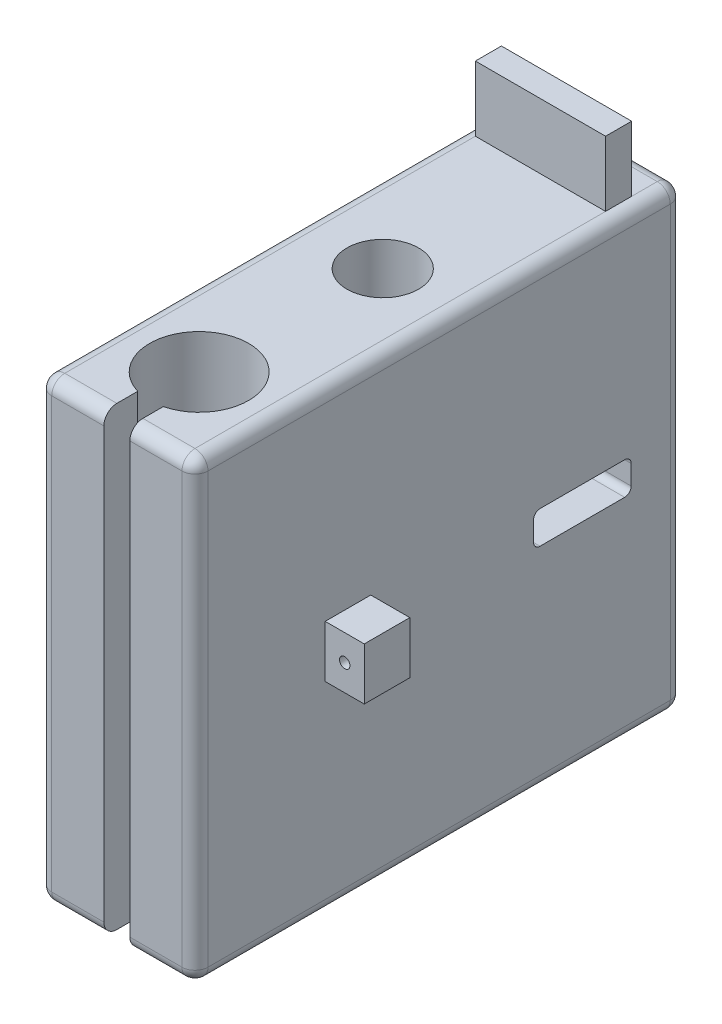
SolidWorks part; units mm, degrees
ref_plane "Front Plane" through (0, 0, 0) normal (0, 0, 1) x (1, 0, 0)
ref_plane "Top Plane" through (0, 0, 0) normal (0, 1, 0) x (1, 0, 0)
ref_plane "Right Plane" through (0, 0, 0) normal (1, 0, 0) x (0, 0, -1)
ref_plane "Plano1" through (-220, 0, 0) normal (1, 0, 0) x (0, 0, -1)
sketch "Esboço1" plane through (-220, 0, 0) normal (1, 0, 0) x (0, 0, -1)
  line L0 (-460.4999, 246.154) -> (-460.4999, 230.354) construction
  line L1 (-465.4999, 248.254) -> (-390.4999, 248.254)
  line L2 (-465.4999, 248.254) -> (-465.4999, 178.254)
  line L3 (-465.4999, 178.254) -> (-390.4999, 178.254)
  line L4 (-390.4999, 248.254) -> (-390.4999, 178.254)
  dimension "D1" = 75
  dimension "D2" = 70
  dimension "D3" = 5
extrude "Ressalto-extrusão1" add sketch "Esboço1" along normal blind 12 and the other way blind 12
sketch "Esboço3" plane through (0, 248.254, 0) normal (0, 1, 0) x (1, 0, 0)
  line L5 (-232, -465.4999) -> (-208, -465.4999) construction
  line L7 (-220, -465.4999) -> (-218, -465.4999)
  line L10 (-218, -465.4999) -> (-218, -460.3692)
  line L11 (-220, -465.4999) -> (-222, -465.4999)
  line L14 (-222, -465.4999) -> (-222, -460.292)
  arc A3 (-218, -460.3692) -> (-222, -460.292) centre (-219.8586, -452.9999) ccw
  circle A8 centre (-219.5085, -425.1499) radius 5.5
  circle A9 centre (-219.5085, -425.1499) radius 5.5
  dimension "D1" = 15.2
  dimension "D3" = 2
  dimension "D4" = 2
  dimension "D2" = 0.5
extrude "Corte-extrusão1" cut sketch "Esboço3" against normal through all
sketch "Esboço4" plane through (0, 0, 390.4999) normal (0, 0, -1) x (-1, 0, 0)
  line L0 (220, 248.254) -> (220, 178.254) construction
  line L1 (232, 248.254) -> (208, 248.254) construction
  line L2 (232, 178.254) -> (208, 178.254) construction
  circle A0 centre (219.8586, 238.254) radius 4.1
  circle A1 centre (219.8586, 188.254) radius 4.1
  dimension "D1" = 8.2
  dimension "D2" = 8.2
extrude "Corte-extrusão2" cut sketch "Esboço4" against normal blind 20
fillet "Filete1" radius 2 14 edges at (-227, 178.254, 465.4999) (-213, 178.254, 465.4999) (-213, 248.254, 465.4999) (-227, 248.254, 465.4999) (-208, 178.254, 427.9999) (-208, 248.254, 427.9999) (-208, 213.254, 465.4999) (-232, 178.254, 427.9999) (-232, 213.254, 465.4999) (-232, 248.254, 427.9999) (-220, 248.254, 390.4999) (-220, 178.254, 390.4999) (-208, 213.254, 390.4999) (-232, 213.254, 390.4999)
sketch "Esboço5" plane through (0, 0, 390.4999) normal (0, 0, -1) x (-1, 0, 0)
  line L8 (213.9984, 195.2586) -> (225.9984, 195.2487)
  line L9 (225.9984, 195.2487) -> (226.0279, 231.2487)
  line L10 (226.0279, 231.2487) -> (214.0279, 231.2586)
  line L11 (214.0279, 231.2586) -> (213.9984, 195.2586)
  line L12 (213.9984, 195.2586) -> (225.9984, 195.2487)
  line L13 (225.9984, 195.2487) -> (226.0279, 231.2487)
  line L14 (226.0279, 231.2487) -> (214.0279, 231.2586)
  line L15 (214.0279, 231.2586) -> (213.9984, 195.2586)
  dimension "D1" = 0
extrude "Corte-extrusão3" cut sketch "Esboço5" against normal blind 29
sketch "Esboço6" plane through (-232, 0, 0) normal (-1, 0, 0) x (0, 0, 1)
  line L0 (392.4999, 213.254) -> (463.4999, 213.254) construction
  line L1 (392.4999, 246.254) -> (392.4999, 180.254) construction
  line L2 (463.4999, 180.254) -> (463.4999, 246.254) construction
  line L3 (398.4999, 213.254) -> (413.4999, 213.254) construction
  line L4 (399.4999, 215.754) -> (412.4999, 215.754)
  line L5 (398.4999, 214.754) -> (398.4999, 211.754)
  line L6 (399.4999, 210.754) -> (412.4999, 210.754)
  line L7 (413.4999, 214.754) -> (413.4999, 211.754)
  arc A0 (412.4999, 215.754) -> (413.4999, 214.754) centre (412.4999, 214.754) cw
  arc A1 (412.4999, 210.754) -> (413.4999, 211.754) centre (412.4999, 211.754) ccw
  arc A2 (398.4999, 211.754) -> (399.4999, 210.754) centre (399.4999, 211.754) ccw
  arc A3 (399.4999, 215.754) -> (398.4999, 214.754) centre (399.4999, 214.754) ccw
  point P14 (413.4999, 215.754)
  point P17 (413.4999, 210.754)
  point P22 (398.4999, 215.754)
  dimension "D4" = 1
  dimension "D1" = 5
  dimension "D2" = 15
  dimension "D3" = 6
extrude "Corte-extrusão4" cut sketch "Esboço6" against normal blind 28
sketch "Esboço7" plane through (-208, 0, 0) normal (1, 0, 0) x (0, 0, -1)
  line L0 (-463.4999, 246.254) -> (-463.4999, 180.254) construction
  line L1 (-445.4999, 217.254) -> (-438.4999, 217.254)
  line L2 (-445.4999, 217.254) -> (-445.4999, 209.254)
  line L3 (-445.4999, 209.254) -> (-438.4999, 209.254)
  line L4 (-438.4999, 217.254) -> (-438.4999, 209.254)
  line L5 (-465.4999, 180.254) -> (-465.4999, 246.254) construction
  point P6 (-463.4999, 213.254)
  point P7 (-445.4999, 213.254)
  dimension "D1" = 7
  dimension "D2" = 8
  dimension "D3" = 20
extrude "Ressalto-extrusão2" add sketch "Esboço7" along normal blind 6 and the other way blind 30
ref_point "Ponto1"
sketch "Esboço9" plane through (0, 0, 445.4999) normal (0, 0, 1) x (1, 0, 0)
  line L0 (-205, 217.254) -> (-205, 209.254) construction
  line L3 (-208, 217.254) -> (-202, 217.254) construction
  line L6 (-208, 209.254) -> (-202, 209.254) construction
  line L7 (-208, 213.254) -> (-202, 213.254) construction
  line L8 (-208, 246.254) -> (-208, 180.254) construction
  line L9 (-202, 217.254) -> (-202, 209.254) construction
hole_wizard "Broca de rosquear para tarraxa de M2x0.41" positions "Esboço13" profile "Esboço14" hole size "M2x0.4" standard "Ansi Metric" end condition through all
sketch "Esboço13" plane through (0, 0, 445.4999) normal (0, 0, 1) x (1, 0, 0)
  line L0 (-205, 217.254) -> (-205, 209.254) construction
  point P0 (-205, 213.254)
sketch "Esboço14" plane through (-205, 213.254, 445.4999) normal (1, 0, 0) x (0, -1, 0)
  line L0 (0, 0) -> (0, 55)
  line L1 (0, 55) -> (0.8, 55)
  line L2 (0.8, 55) -> (0.8, 0)
  line L5 (0.8, 0) -> (0, 0)
  line L11 (0, -6.35) -> (0, 107.95) construction
  dimension "Thru Hole Dia." = 1.6
  dimension "Thru Hole Depth" = 55
sketch "Esboço15" plane through (0, 0, 445.4999) normal (0, 0, 1) x (1, 0, 0)
  line L0 (-235, 217.254) -> (-235, 209.254) construction
  line L1 (-238, 217.254) -> (-232, 217.254) construction
  line L2 (-238, 209.254) -> (-232, 209.254) construction
  line L3 (-238, 213.254) -> (-232, 213.254) construction
  line L4 (-238, 217.254) -> (-238, 209.254) construction
  line L5 (-232, 180.254) -> (-232, 246.254) construction
hole_wizard "Broca de rosquear para tarraxa de M2x0.42" positions "Esboço16" profile "Esboço17" hole size "M2x0.4" standard "Ansi Metric" end condition through all
sketch "Esboço16" plane through (0, 0, 445.4999) normal (0, 0, 1) x (1, 0, 0)
  line L0 (-235, 217.254) -> (-235, 209.254) construction
  point P0 (-235, 213.254)
sketch "Esboço17" plane through (-235, 213.254, 445.4999) normal (1, 0, 0) x (0, -1, 0)
  line L0 (0, 0) -> (0, 55)
  line L1 (0, 55) -> (0.8, 55)
  line L2 (0.8, 55) -> (0.8, 0)
  line L5 (0.8, 0) -> (0, 0)
  line L11 (0, -6.35) -> (0, 107.95) construction
  dimension "Thru Hole Dia." = 1.6
  dimension "Thru Hole Depth" = 55
sketch "Esboço18" plane through (0, 248.254, 0) normal (0, 1, 0) x (1, 0, 0)
  line L0 (-230, -392.4999) -> (-230, -463.4999) construction
  line L1 (-230, -396.4346) -> (-210, -396.4346)
  line L2 (-230, -396.4346) -> (-230, -400.4346)
  line L3 (-230, -400.4346) -> (-210, -400.4346)
  line L4 (-210, -396.4346) -> (-210, -400.4346)
  line L5 (-210, -463.4999) -> (-210, -392.4999) construction
  dimension "D1" = 4
extrude "Ressalto-extrusão3" add sketch "Esboço18" along normal blind 10
